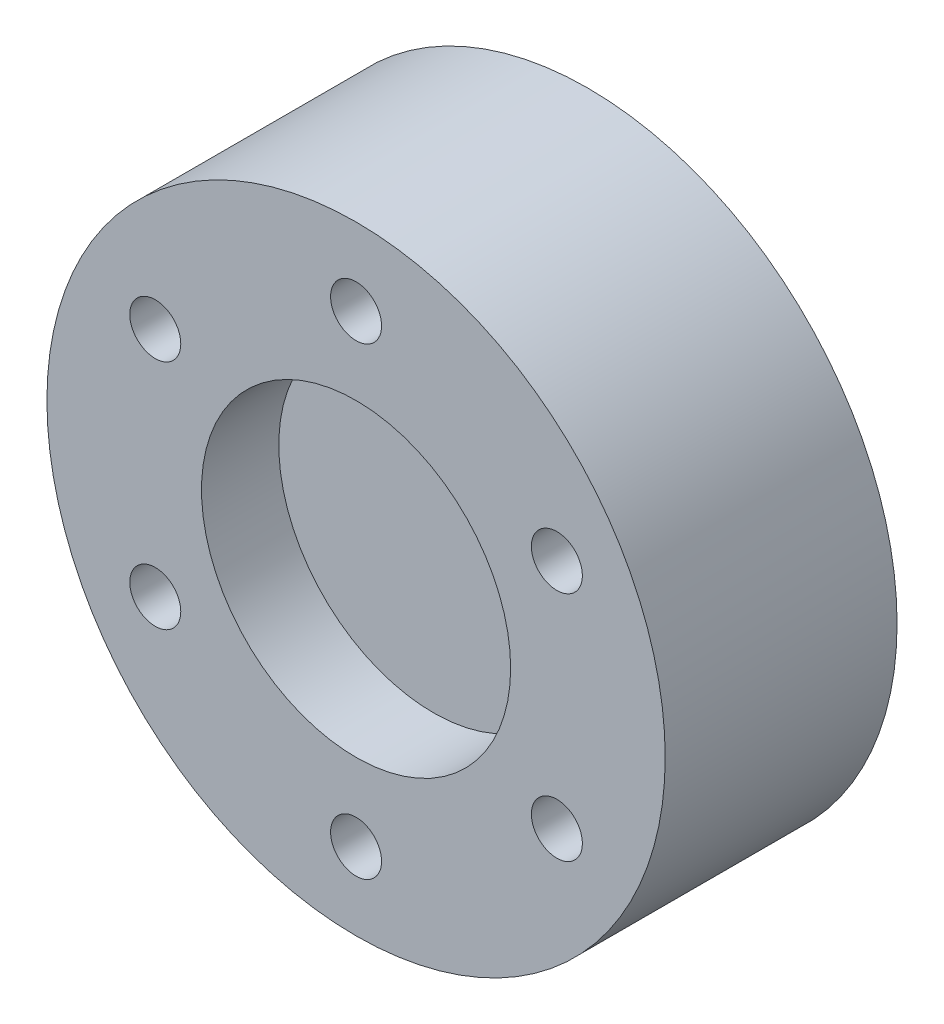
SolidWorks part; units mm, degrees
ref_plane "Front Plane" through (0, 0, 0) normal (0, 0, 1) x (1, 0, 0)
ref_plane "Top Plane" through (0, 0, 0) normal (0, 1, 0) x (1, 0, 0)
ref_plane "Right Plane" through (0, 0, 0) normal (1, 0, 0) x (0, 0, -1)
sketch "Sketch1" plane through (0, 0, 0) normal (0, 0, 1) x (1, 0, 0)
  circle A0 centre (0, 0) radius 20
  dimension "D1" = 40
extrude "Boss-Extrude1" add sketch "Sketch1" along normal blind 15
sketch "Sketch2" plane through (0, 0, 15) normal (0, 0, 1) x (1, 0, 0)
  circle A0 centre (0, 0) radius 10
extrude "Cut-Extrude1" cut sketch "Sketch2" against normal blind 5
hole_wizard "M4x0.7 Tapped Hole1" positions "Sketch3" profile "Sketch4" tap size "M4x0.7" standard "ANSI Metric"
sketch "Sketch3" plane through (0, 0, 15) normal (0, 0, 1) x (1, 0, 0)
  point P0 (0, 15)
  point P4 (0, 0)
  dimension "D1" = 15
sketch "Sketch4" plane through (0, 15, 15) normal (1, 0, 0) x (0, -1, 0)
  line L0 (0, 0) -> (0, 8.0914)
  line L1 (0, 8.0914) -> (1.65, 7.1)
  line L2 (1.65, 7.1) -> (1.65, 0)
  line L5 (1.65, 0) -> (0, 0)
  line L10 (0, 8.0914) -> (-1.65, 7.1) construction
  line L11 (0, -6.35) -> (0, 107.95) construction
  dimension "Tap Drill Dia." = 3.3
  dimension "Tap Drill Depth" = 7.1
  dimension "Drill Angle" = 118
cosmetic thread "Hole Thread1" parameters "D1"=5, "D2"=4
pattern_circular "CirPattern2" count 6 over 360 about axis through (0, 0, 10) along (0, 0, 1) of "M4x0.7 Tapped Hole1"
cosmetic thread "Hole Thread2" parameters "D1"=5, "D2"=4
cosmetic thread "Hole Thread3" parameters "D1"=5, "D2"=4
cosmetic thread "Hole Thread4" parameters "D1"=5, "D2"=4
cosmetic thread "Hole Thread5" parameters "D1"=5, "D2"=4
cosmetic thread "Hole Thread6" parameters "D1"=5, "D2"=4
sketch "Sketch5" plane through (0, 0, 0) normal (0, 0, -1) x (-1, 0, 0)
  circle A0 centre (0, 0) radius 17.5
extrude "Cut-Extrude2" cut sketch "Sketch5" against normal blind 3
